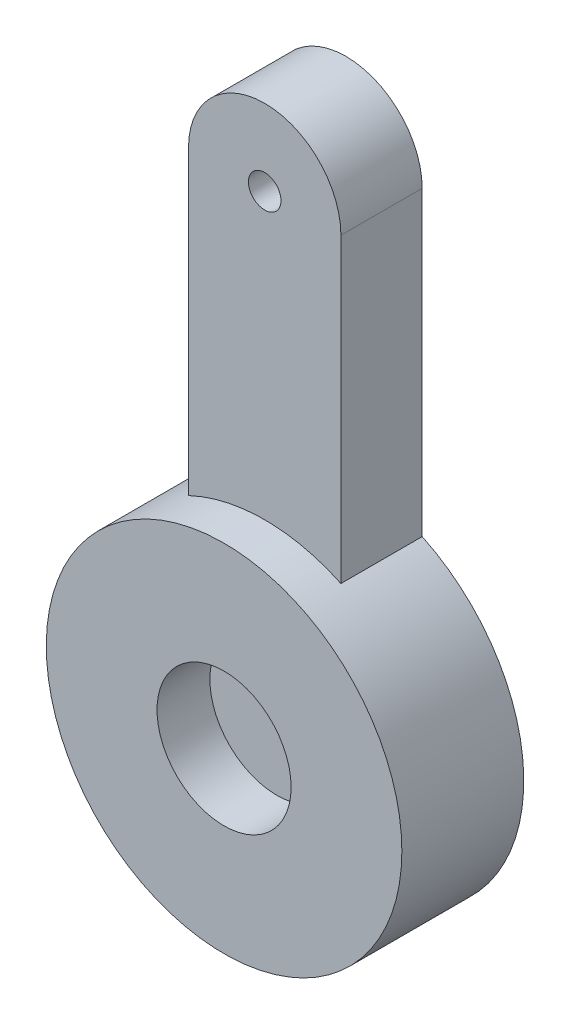
SolidWorks part; units mm, degrees
ref_plane "Alzado" through (0, 0, 0) normal (0, 0, 1) x (1, 0, 0)
ref_plane "Planta" through (0, 0, 0) normal (0, 1, 0) x (1, 0, 0)
ref_plane "Vista lateral" through (0, 0, 0) normal (1, 0, 0) x (0, 0, -1)
sketch "Croquis1" plane through (0, 0, 0) normal (0, 0, 1) x (1, 0, 0)
  circle A0 centre (0, 0) radius 17.5
  dimension "D1" = 35
extrude "Saliente-Extruir1" add sketch "Croquis1" along normal blind 12
sketch "Croquis2" plane through (0, 0, 0) normal (0, 1, 0) x (1, 0, 0)
  line L0 (-7.5, 0) -> (7.5, 0)
  line L1 (-7.5, 0) -> (-7.5, -8)
  line L2 (7.5, 0) -> (7.5, -8)
  line L3 (-7.5, -8) -> (7.5, -8)
  line L4 (17.5, 0) -> (-17.5, 0) construction
  point P6 (-6.9987, -7.2141)
  point P7 (0, 0)
  dimension "D1" = 15
  dimension "D2" = 8
extrude "Saliente-Extruir2" add sketch "Croquis2" along normal blind 38
sketch "Croquis3" plane through (0, 38, 0) normal (0, 1, 0) x (1, 0, 0)
  line L4 (-7.5, 0) -> (-7.5, -8)
  line L5 (-7.5, -8) -> (7.5, -8)
  line L6 (7.5, -8) -> (7.5, 0)
  line L7 (7.5, 0) -> (-7.5, 0)
  line L8 (-7.5, 0) -> (-7.5, -8)
  line L9 (-7.5, -8) -> (7.5, -8)
  line L10 (7.5, -8) -> (7.5, 0)
  line L11 (7.5, 0) -> (-7.5, 0)
  dimension "D1" = 0
extrude "Saliente-Extruir3" add sketch "Croquis3" along normal blind 15
fillet "Redondeo1" 2 edges at (-7.5, 53, 4) (7.5, 53, 4) type full round first side face at (-7.5, 34.4057, 4) second side face at (7.5, 34.4057, 4) middle face at (0, 53, 4)
sketch "Croquis4" plane through (0, 0, 12) normal (0, 0, 1) x (1, 0, 0)
  circle A0 centre (0, 0) radius 6.6
  dimension "D1" = 13.2
extrude "Cortar-Extruir1" cut sketch "Croquis4" against normal blind 5.2
sketch "Croquis5" plane through (0, 0, 0) normal (0, 0, -1) x (-1, 0, 0)
  circle A0 centre (0, 0) radius 6.6
  dimension "D1" = 13.2
extrude "Cortar-Extruir2" cut sketch "Croquis5" against normal blind 5.2
sketch "Croquis7" plane through (0, 0, 0) normal (0, 0, -1) x (-1, 0, 0)
  circle A0 centre (0, 45.5) radius 5
  dimension "D1" = 10
extrude "Saliente-Extruir4" add sketch "Croquis7" along normal blind 1.5
sketch "Croquis6" plane through (0, 0, 0) normal (0, 0, -1) x (-1, 0, 0)
  circle A0 centre (0, 45.5) radius 1.6
  dimension "D1" = 3.2
extrude "Cortar-Extruir3" cut sketch "Croquis6" against normal through all both and the other way through all
ref_point "Punto1"
ref_point "Punto2"
sketch "Croquis8" plane through (0, 0, 0) normal (0, 1, 0) x (1, 0, 0)
  line L0 (0, -12) -> (0, 0)
ref_point "Punto3" parameters "D1"=6
